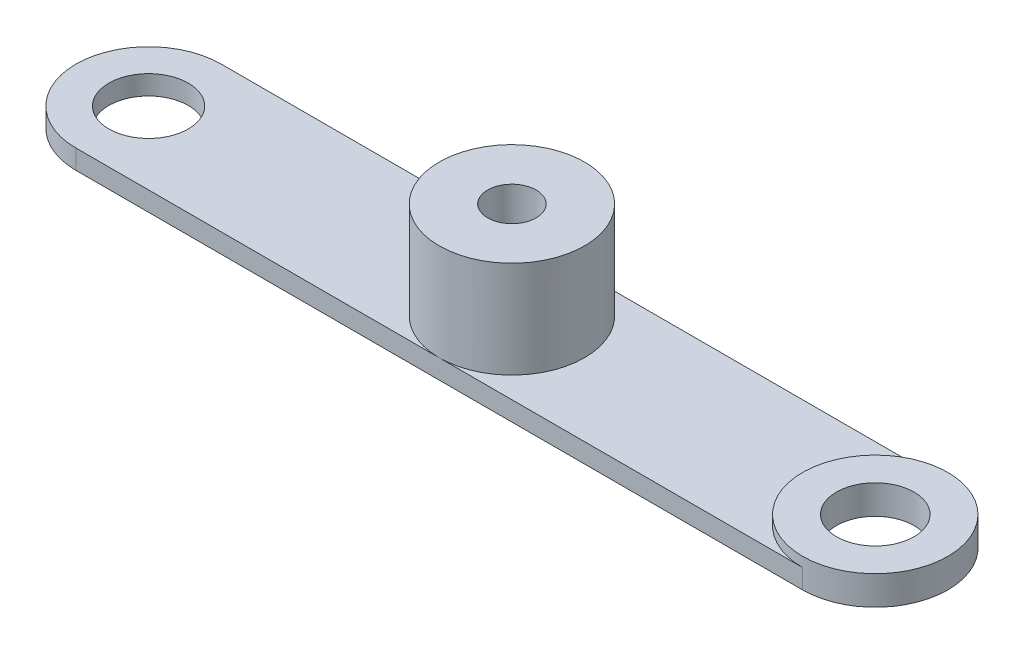
SolidWorks part; units mm, degrees
ref_plane "Front Plane" through (0, 0, 0) normal (0, 0, 1) x (1, 0, 0)
ref_plane "Top Plane" through (0, 0, 0) normal (0, 1, 0) x (1, 0, 0)
ref_plane "Right Plane" through (0, 0, 0) normal (1, 0, 0) x (0, 0, -1)
sketch "Sketch1" plane through (0, 0, 0) normal (0, 1, 0) x (1, 0, 0)
  line L0 (-37.5, 0) -> (37.5, 0) construction
  line L1 (-37.5, 7.5) -> (37.5, 7.5)
  line L2 (-37.5, -7.5) -> (37.5, -7.5)
  arc A0 (-37.5, 7.5) -> (-37.5, -7.5) centre (-37.5, 0) ccw
  arc A1 (37.5, -7.5) -> (37.5, 7.5) centre (37.5, 0) ccw
  circle A2 centre (-37.5, 0) radius 4.1
  circle A3 centre (37.5, 0) radius 4
  point P2 (0, 0)
  dimension "D2" = 7.5
  dimension "D3" = 4.1
  dimension "D4" = 4
  dimension "D1" = 75
extrude "Boss-Extrude1" add sketch "Sketch1" along normal blind 2
sketch "Sketch3" plane through (0, 2, 0) normal (0, 1, 0) x (1, 0, 0)
  circle A0 centre (0, 0) radius 7.5
  dimension "D1" = 7.5
extrude "Boss-Extrude3" add sketch "Sketch3" along normal blind 10
sketch "Sketch4" plane through (0, 12, 0) normal (0, 1, 0) x (1, 0, 0)
  circle A0 centre (0, 0) radius 2.5
  dimension "D1" = 5
extrude "Cut-Extrude1" cut sketch "Sketch4" against normal through all
sketch "Sketch5" plane through (0, 2, 0) normal (0, 1, 0) x (1, 0, 0)
  circle A0 centre (37.5, 0) radius 7.5
  circle A1 centre (37.5, 0) radius 4
  dimension "D1" = 7.5
  dimension "D2" = 4
extrude "Boss-Extrude4" add sketch "Sketch5" along normal blind 1
